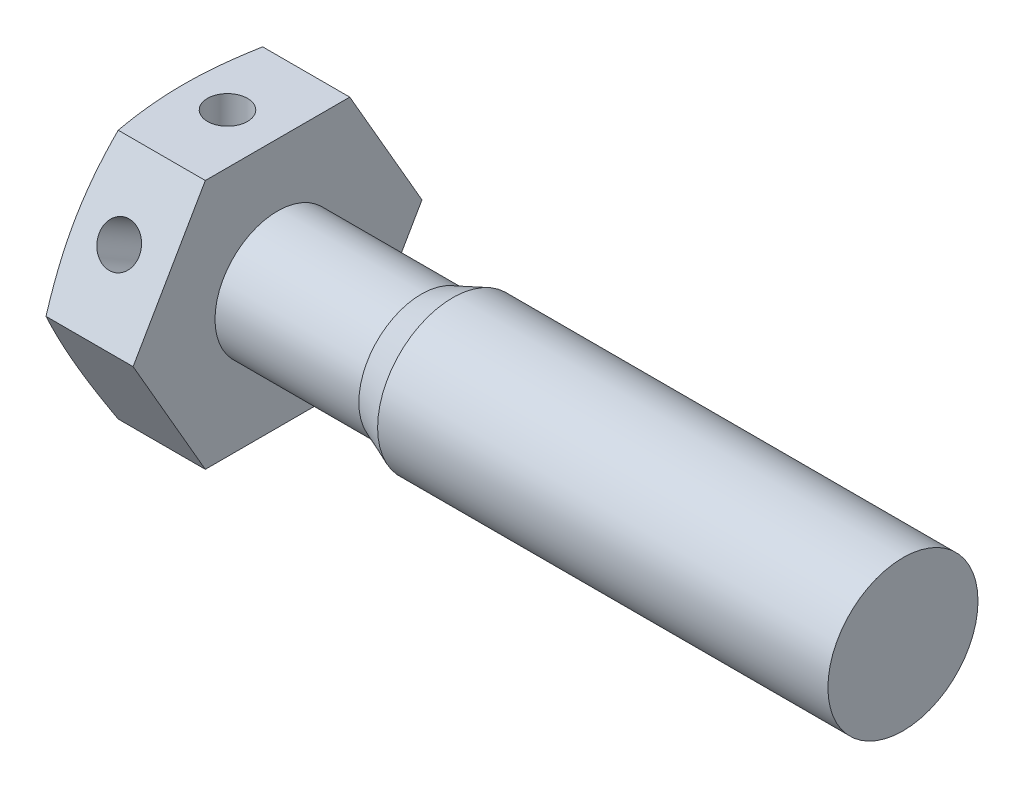
SolidWorks part; units mm, degrees
ref_plane "Front" through (0, 0, 0) normal (0, 0, 1) x (1, 0, 0)
ref_plane "Top" through (0, 0, 0) normal (0, 1, 0) x (1, 0, 0)
ref_plane "Right" through (0, 0, 0) normal (1, 0, 0) x (0, 0, -1)
sketch "Sketch1" plane through (0, 0, 0) normal (1, 0, 0) x (0, 0, -1)
  line L1 (5.7735, 0) -> (2.8868, 5)
  line L2 (2.8868, 5) -> (-2.8868, 5)
  line L3 (-2.8868, 5) -> (-5.7735, 0)
  line L4 (-5.7735, 0) -> (-2.8868, -5)
  line L5 (-2.8868, -5) -> (2.8868, -5)
  line L6 (2.8868, -5) -> (5.7735, 0)
  circle A0 centre (0, 0) radius 5 construction
  dimension "s" = 10
extrude "BaseHead" add sketch "Sketch1" along normal blind 4
ref_plane "Plane1" through (11, 0, 0) normal (1, 0, 0) x (0, 0, -1)
sketch "Sketch2" plane through (4, 0, 0) normal (1, 0, 0) x (0, 0, -1)
  circle A0 centre (0, 0) radius 3
extrude "BaseBody" add sketch "Sketch2" along normal blind 25
cosmetic thread "ThreadCosmetic1" [suppressed] parameters "b"=18, "D2"=4.917
sketch "Sketch3" plane through (3.1612, 0, 2.6123) normal (0, 1, 0) x (0, 0, -1)
  line L0 (2.6123, 5.2326) -> (2.6123, 1.6388) construction
  line L2 (8.3858, 3.1612) -> (8.3858, 2.6431)
  line L3 (8.3858, 2.6431) -> (6.9623, 3.1612)
  line L5 (6.9623, 3.1612) -> (8.3858, 3.1612)
  dimension "D1" = 20
  dimension "dw" = 8.7
revolve "HeadChamfer" cut sketch "Sketch3" angle 360 about L0
sketch "Sketch4" plane through (0, 0, 0) normal (-1, 0, 0) x (0, 0, 1)
  circle A0 centre (0, 0) radius 3.4
  dimension "da" = 6.8
extrude "Cut-Extrude1" cut sketch "Sketch4" against normal blind 0.8
sketch "Sketch5" plane through (-2.9296, 0, 7.9296) normal (0, 1, 0) x (0, 0, -1)
  line L0 (7.9296, -0.2325) -> (7.9296, -16.4861) construction
  line L1 (7.9296, -31.9296) -> (7.9296, -6.9296) construction
  line L2 (10.9296, -13.9296) -> (10.4296, -12.6796)
  line L3 (4.9296, -31.9296) -> (10.9296, -31.9296) construction
  line L4 (10.4296, -12.6796) -> (10.4296, -6.9296)
  line L5 (10.9296, -31.9296) -> (10.9296, -6.9296) construction
  line L6 (10.4296, -6.9296) -> (12.9296, -6.9296)
  line L7 (12.9296, -6.9296) -> (12.9296, -13.9296)
  line L8 (12.9296, -13.9296) -> (10.9296, -13.9296)
  line L9 (13.7031, -6.9296) -> (10.8164, -6.9296) construction
  dimension "D4" = 10
  dimension "D3" = 18
revolve "Cut-Revolve1" cut sketch "Sketch5" angle 360 about L0
fillet "HeadFillet" [suppressed] radius 0.25
sketch "Sketch6" plane through (0, 0, 0) normal (0, 1, 0) x (1, 0, 0)
  line L0 (-2.6972, 0) -> (13.5564, 0) construction
  line L1 (4, 5.7735) -> (4, 2.8868) construction
  circle A0 centre (2, 0) radius 0.8
  dimension "d1" = 1.6
  dimension "h" = 2
extrude "Hole" cut sketch "Sketch6" against normal through all and the other way through all
pattern_circular "CirPattern1" count 2 over 60 about axis through (-2.6972, 0, 0) along (1, 0, 0) of "Hole"
sketch "Sketch7" plane through (0, 0, 0) normal (0, 0, 1) x (1, 0, 0)
  line L0 (28.7293, 3.2) -> (29.2707, 3.2)
  line L1 (29.2707, 3.2) -> (29.2708, 3)
  line L2 (29.2708, 3) -> (29, 2.531)
  line L3 (28.7293, 3) -> (29, 2.531)
  line L4 (28.7293, 3.2) -> (28.7293, 3)
  line L5 (28.8635, 0) -> (0, 0) construction
  line L6 (28.7293, 3) -> (29.2708, 3) construction
  line L7 (29, 3) -> (29, 2.531) construction
  line L8 (29, -3) -> (29, 3) construction
  line L9 (29, 3) -> (11, 3) construction
  point P5 (29, 3.2)
  dimension "D1" = 0.2
  dimension "D2" = 0.5415
revolve "Cut-Revolve10" [suppressed] cut sketch "Sketch7" angle 360 about L5
pattern_linear "LPattern10" [suppressed] count 28 spacing 0.6498 along (-1, 0, 0) of bodies 108
equation "\"D1@Cut-Extrude1\" = 0.2 * \"k@BaseHead\""
equation "\"b@ThreadCosmetic1\" = \"l@BaseBody\" - \"lg@Plane1\""
equation "\"D4@Sketch5\" = 2 * \"ds@Sketch5\""
equation "\"D3@Sketch5\" =\"l@BaseBody\" - \"lg@Plane1\""
equation "\"D2@Sketch7\" =  ( \"d@Sketch2\" - \"D2@ThreadCosmetic1\" )  / 2"
equation "\"D3@LPattern10\" = \"D2@Sketch7\" * 1.2"
equation "\"D1@LPattern10\" = \"b@ThreadCosmetic1\" / \"D3@LPattern10\""
